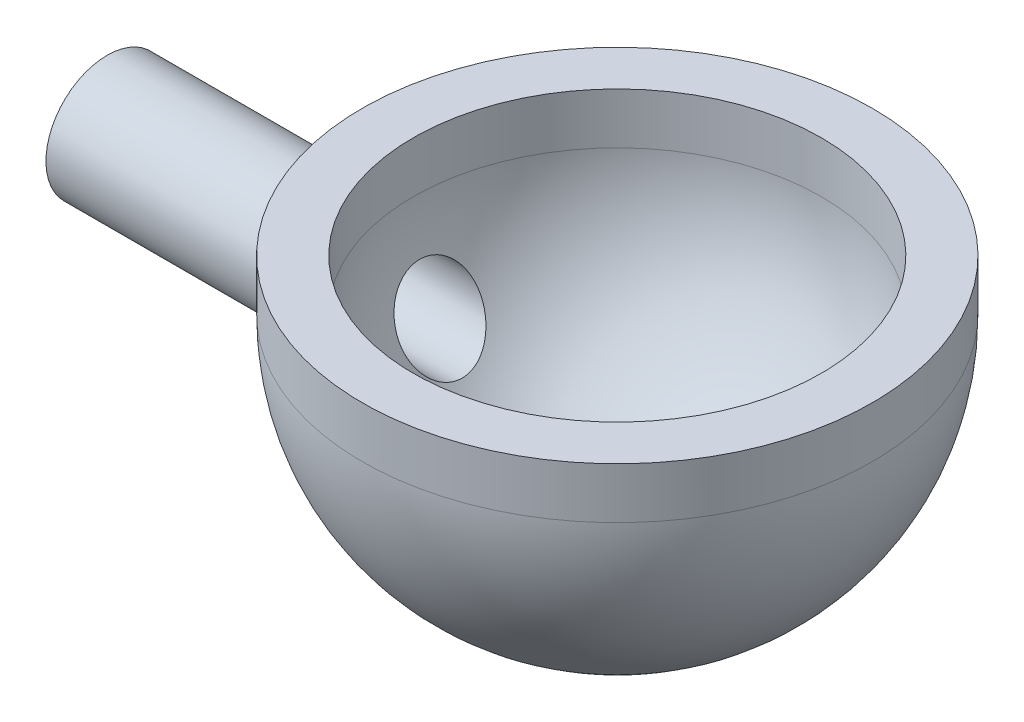
SolidWorks part; units mm, degrees
material "1023 Carbon Steel Sheet (SS)"
ref_plane "Front Plane" through (0, 0, 0) normal (0, 0, 1) x (1, 0, 0)
ref_plane "Top Plane" through (0, 0, 0) normal (0, 1, 0) x (1, 0, 0)
ref_plane "Right Plane" through (0, 0, 0) normal (1, 0, 0) x (0, 0, -1)
sketch "Sketch1" plane through (0, 0, 0) normal (0, 0, 1) x (1, 0, 0)
  line L0 (20, 0) -> (20, -5)
  line L1 (0, 18.5331) -> (0, 32.2934) construction
  line L2 (25, 0) -> (25, -5)
  line L3 (20, 0) -> (25, 0)
  line L4 (0, -25) -> (0, -30)
  line L5 (55, 0) -> (-55, 0) construction
  arc A0 (20, -5) -> (0, -25) centre (0, -5) cw
  arc A1 (25, -5) -> (0, -30) centre (0, -5) cw
  dimension "D1" = 40
  dimension "D2" = 5
  dimension "D3" = 5
revolve "Revolve1" add sketch "Sketch1" angle 360 about L1
ref_plane "Plane1" through (-50, 0, 0) normal (1, 0, 0) x (0, 0, -1)
sketch "Sketch2" plane through (-50, 0, 0) normal (1, 0, 0) x (0, 0, -1)
  line L0 (38.5, 0) -> (-38.5, 0) construction
  line L1 (0, 6.3515) -> (0, 2.2794) construction
  circle A0 centre (0, -14) radius 6
  dimension "D1" = 12
  dimension "D3" = 14
extrude "Boss-Extrude1" add sketch "Sketch2" along normal up to next
sketch "Sketch4" plane through (-50, 0, 0) normal (-1, 0, 0) x (0, 0, 1)
  circle A0 centre (0, -14) radius 4
  circle A1 centre (0, -14) radius 6 construction
  dimension "D1" = 2
extrude "Cut-Extrude1" cut sketch "Sketch4" against normal up to next
